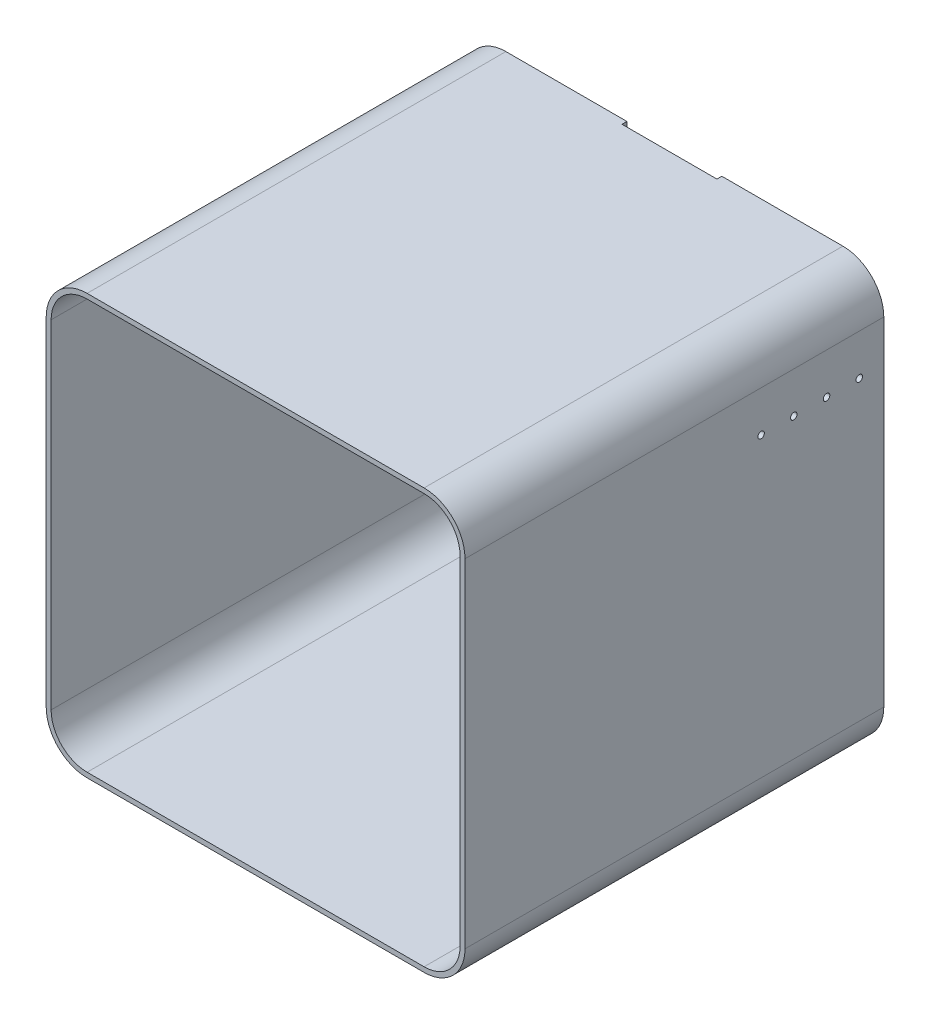
SolidWorks part; units mm, degrees
material "Pine"
ref_plane "Front Plane" through (0, 0, 0) normal (0, 0, 1) x (1, 0, 0)
ref_plane "Top Plane" through (0, 0, 0) normal (0, 1, 0) x (1, 0, 0)
ref_plane "Right Plane" through (0, 0, 0) normal (1, 0, 0) x (0, 0, -1)
sketch "Sketch1" plane through (0, 0, 0) normal (0, 0, 1) x (1, 0, 0)
  line L1 (44, 0) -> (456, 0)
  line L2 (0, 44) -> (0, 457)
  line L3 (44, 501) -> (456, 501)
  line L4 (500, 44) -> (500, 457)
  arc A0 (0, 457) -> (44, 501) centre (44, 457) cw
  arc A1 (456, 501) -> (500, 457) centre (456, 457) cw
  arc A2 (456, 0) -> (500, 44) centre (456, 44) ccw
  arc A3 (44, 0) -> (0, 44) centre (44, 44) cw
  point P9 (0, 501)
  point P12 (500, 501)
  point P15 (500, 0)
  point P18 (0, 0)
  dimension "D3" = 44
  dimension "D4" = 44
  dimension "D5" = 44
  dimension "D6" = 44
  dimension "D1" = 500
  dimension "D2" = 501
extrude "Extrude-Thin1" add sketch "Sketch1" against normal blind 512 thin contours A0 L3 A1 L4 A2 L1 A3 L2 thin type one direction wall 6
sketch "Sketch3" plane through (506, 0, 0) normal (1, 0, 0) x (0, 0, -1)
  line L0 (512, 44) -> (512, 457) construction
  line L1 (512, 457) -> (0, 457) construction
  circle A0 centre (482, 407) radius 4
  dimension "D1" = 30
  dimension "D2" = 8
  dimension "D3" = 50
extrude "Cut-Extrude1" cut sketch "Sketch3" against normal blind 10
pattern_linear "LPattern1" count 4 spacing 40 along (0, 0, 1) of "Cut-Extrude1"
sketch "Sketch4" plane through (0, 0, -512) normal (0, 0, -1) x (-1, 0, 0)
  line L0 (-44, 507) -> (-456, 507) construction
  line L1 (-44, 501) -> (-456, 501) construction
  line L2 (-308, 507) -> (-192, 507)
  line L3 (-308, 507) -> (-308, 501)
  line L4 (-308, 501) -> (-192, 501)
  line L5 (-192, 507) -> (-192, 501)
  dimension "D1" = 6
  dimension "D2" = 148
  dimension "D3" = 148
extrude "Cut-Extrude2" cut sketch "Sketch4" against normal blind 6
